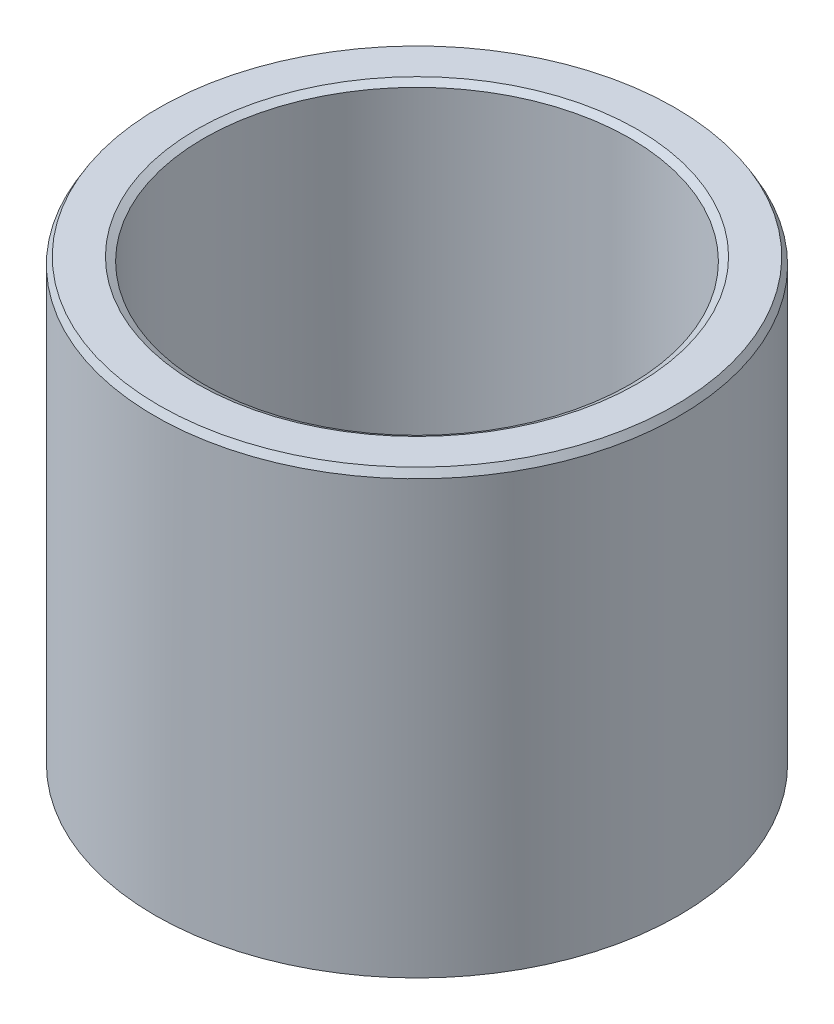
SolidWorks part; units mm, degrees
ref_plane "Front Plane" through (0, 0, 0) normal (0, 0, 1) x (1, 0, 0)
ref_plane "Top Plane" through (0, 0, 0) normal (0, 1, 0) x (1, 0, 0)
ref_plane "Right Plane" through (0, 0, 0) normal (1, 0, 0) x (0, 0, -1)
sketch "Sketch1" plane through (0, 0, 0) normal (0, 1, 0) x (1, 0, 0)
  circle A0 centre (0, 0) radius 47.5
  dimension "SLEEVE_OD" = 95
extrude "Boss-Extrude1" add sketch "Sketch1" along normal blind 80.4045
sketch "Sketch2" plane through (0, 0, 0) normal (0, 1, 0) x (1, 0, 0)
  circle A0 centre (0, 0) radius 38.6318
  dimension "BORE_D" = 77.2635
extrude "Cut-Extrude1" cut sketch "Sketch2" along normal through all
chamfer "Chamfer1" distance 1.3016 angle 30 4 edges at (0, 80.4045, 38.6318) (0, 0, 38.6318) (0, 0, 47.5) (0, 80.4045, 47.5) first distance on face at (0, 80.4045, 38.6318) first distance on face at (0, 0, 38.6318) first distance on face at (0, 80.4045, 47.5)
